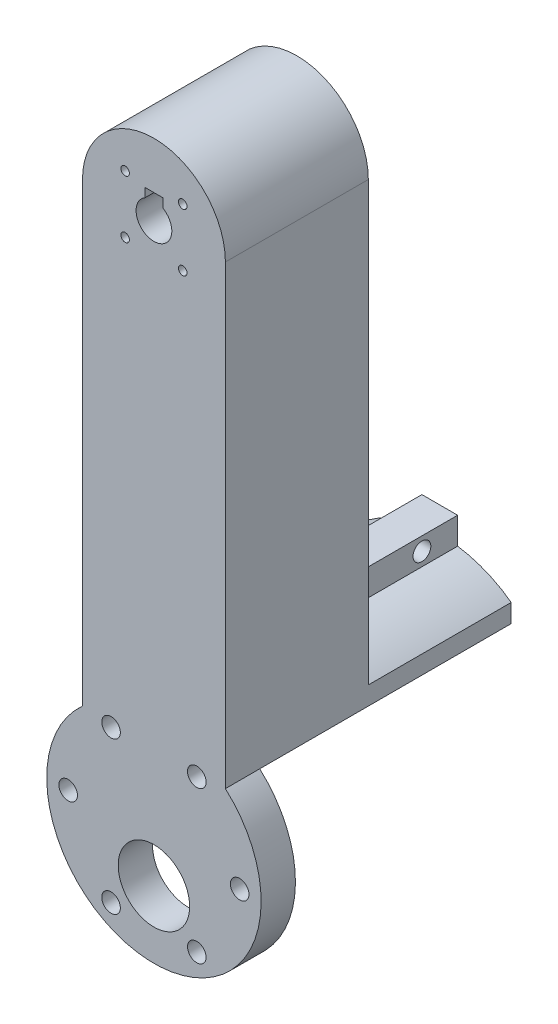
SolidWorks part; units mm, degrees
ref_plane "Front Plane" through (0, 0, 0) normal (0, 0, 1) x (1, 0, 0)
ref_plane "Top Plane" through (0, 0, 0) normal (0, 1, 0) x (1, 0, 0)
ref_plane "Right Plane" through (0, 0, 0) normal (1, 0, 0) x (0, 0, -1)
sketch "Sketch1" plane through (0, 0, 0) normal (0, 0, 1) x (1, 0, 0)
  line L0 (-5.1187, 55.9187) -> (5.1187, 45.6813) construction
  line L2 (12.7, 50.8) -> (12.7, -50.8)
  line L4 (-12.7, 50.8) -> (-12.7, -50.8)
  line L5 (12.7, 50.8) -> (-12.7, -50.8) construction
  line L6 (12.7, -50.8) -> (-12.7, 50.8) construction
  line L7 (5.1187, 55.9187) -> (-5.1187, 45.6813) construction
  line L8 (0, 50.8) -> (0, 51.7208) construction
  arc A0 (-12.7, 50.8) -> (12.7, 50.8) centre (0, 50.8) cw
  arc A1 (12.7, -50.8) -> (-12.7, -50.8) centre (0, -50.8) cw
  circle A2 centre (0, 50.8) radius 3.175
  circle A3 centre (-5.1187, 55.9187) radius 0.762
  circle A4 centre (5.1187, 55.9187) radius 0.762
  circle A5 centre (5.1187, 45.6813) radius 0.762
  circle A6 centre (-5.1187, 45.6813) radius 0.762
  point P0 (0, 0)
  point P14 (0, 50.8)
  point P15 (0, 50.8)
  point P20 (0, 0)
  point P21 (0, 0)
  dimension "D3" = 6.35
  dimension "D6" = 1.524
  dimension "D1" = 25.4
  dimension "D2" = 101.6
  dimension "D4" = 45
  dimension "D5" = 14.478
extrude "Boss-Extrude1" add sketch "Sketch1" along normal blind 25.4
sketch "Sketch2" plane through (0, 0, 0) normal (0, 0, -1) x (-1, 0, 0)
  circle A0 centre (0, -44.45) radius 19.05
  circle A1 centre (0, 50.8) radius 3.175 construction
  arc A2 (-12.7, -50.8) -> (12.7, -50.8) centre (0, -50.8) ccw construction
  circle A3 centre (0, 50.8) radius 3.175
  point P5 (0, 0)
  point P10 (0, 0)
  point P11 (0, 0)
  point P12 (0, 0)
  point P13 (0, 0)
  dimension "D1" = 38.1
extrude "Boss-Extrude2" add sketch "Sketch2" against normal blind 25.4
sketch "Sketch4" plane through (0, 0, 25.4) normal (0, 0, 1) x (1, 0, 0)
  circle A0 centre (0, -44.45) radius 19.05
  arc A1 (-12.7, -30.251) -> (12.7, -30.251) centre (0, -44.45) ccw construction
  point P5 (0, 0)
  point P6 (0, 0)
  point P7 (0, 0)
  point P9 (0, 0)
  point P10 (0, 0)
  dimension "D1" = 38.1
sketch "Sketch3" plane through (0, 0, 25.4) normal (0, 0, 1) x (1, 0, 0)
  line L0 (-15.24, -44.45) -> (15.24, -44.45) construction
  line L1 (15.24, -44.45) -> (7.62, -30.9593) construction
  line L2 (-15.24, -44.45) -> (-7.62, -30.9593) construction
  line L3 (-15.24, -44.45) -> (-7.62, -57.9407) construction
  line L4 (15.24, -44.45) -> (7.62, -57.9407) construction
  line L5 (0, -44.45) -> (0, 0) construction
  circle A0 centre (-7.62, -30.9593) radius 1.651
  circle A1 centre (7.62, -30.9593) radius 1.651
  circle A2 centre (-15.24, -44.45) radius 1.651
  circle A3 centre (-7.62, -57.9407) radius 1.651
  circle A4 centre (7.62, -57.9407) radius 1.651
  circle A5 centre (15.24, -44.45) radius 1.651
  point P10 (0, -44.45)
  dimension "D5" = 3.302
  dimension "D1" = 30.48
  dimension "D2" = 15.494
  dimension "D3" = 30.988
  dimension "D4" = 15.24
extrude "Cut-Extrude1" cut sketch "Sketch3" against normal blind 25.4
sketch "Sketch5" plane through (0, 0, 25.4) normal (0, 0, 1) x (1, 0, 0)
  circle A0 centre (0, -51.562) radius 6.35
  point P2 (0, 0)
  dimension "D1" = 12.7
  dimension "D2" = 7.112
extrude "Cut-Extrude2" cut sketch "Sketch5" against normal blind 25.4
sketch "Sketch6" plane through (0, 0, 0) normal (0, 0, -1) x (-1, 0, 0)
  line L1 (-1.5875, 55.1371) -> (1.5875, 55.1371)
  line L2 (-1.5875, 55.1371) -> (-1.5875, 53.5496)
  line L3 (-1.5875, 53.5496) -> (1.5875, 53.5496)
  line L4 (1.5875, 55.1371) -> (1.5875, 53.5496)
  circle A1 centre (0, 50.8) radius 3.175 construction
  point P4 (0, 0)
  point P5 (0, 0)
  point P9 (0, 0)
  dimension "D1" = 3.175
  dimension "D2" = 1.5875
extrude "Cut-Extrude3" cut sketch "Sketch6" against normal blind 25.4
extrude "Cut-Extrude6" cut sketch "Sketch2<2>" against normal up to surface (25.4 mm away) contours A3 up to face at (0, 54.3434, 25.4)
sketch "Sketch2<2>" plane through (0, 0, 0) normal (0, 0, -1) x (-1, 0, 0) same geometry as "Sketch2"
sketch "Sketch8" plane through (0, 0, 0) normal (0, 0, -1) x (-1, 0, 0)
  circle A0 centre (0, -44.45) radius 19.05
  arc A1 (-1.5875, 53.5496) -> (1.5875, 53.5496) centre (0, 50.8) ccw construction
  arc A2 (-1.5875, 53.5496) -> (1.5875, 53.5496) centre (0, 50.8) ccw
  point P3 (0, 0)
  point P7 (0, 0)
  circle M6 centre (0, -51.562) radius 6.35
  circle M7 centre (7.62, -30.9593) radius 1.651
  circle M8 centre (-15.24, -44.45) radius 1.651
  circle M9 centre (-7.62, -57.9407) radius 1.651
  circle M10 centre (7.62, -57.9407) radius 1.651
  circle M11 centre (15.24, -44.45) radius 1.651
  circle M12 centre (-7.62, -30.9593) radius 1.651
  arc M14 (-12.7, -30.251) -> (12.7, -30.251) centre (0, -44.45) ccw
  dimension "D1" = 38.1
extrude "Cut-Extrude4" cut sketch "Sketch8" against normal blind 19.3 contours A0 M14 M6 M8 M10 M12 M11 M9 M7 | M7 | M12 | M8 | M9 | M6 | M10 | M11 region at (0, -43.5135, 0) region at (0, -51.562, 0) region at (-7.62, -30.9593, 0) region at (15.24, -44.45, 0) region at (7.62, -57.9407, 0) region at (-7.62, -57.9407, 0) region at (-15.24, -44.45, 0) region at (7.62, -30.9593, 0)
sketch "Sketch9" plane through (0, 0, 0) normal (0, 0, -1) x (-1, 0, 0)
  line L0 (12.7, 50.8) -> (12.7, -30.251) construction
  line L1 (-12.7, -30.251) -> (-12.7, 50.8) construction
  line L2 (-12.7, -30.251) -> (-12.7, -26.9904)
  line L3 (12.7, -30.251) -> (12.7, -26.9904)
  arc A0 (-12.7, -30.251) -> (12.7, -30.251) centre (0, -44.45) cw
  arc A1 (-12.7, -26.9904) -> (12.7, -26.9904) centre (0, -44.45) cw
  dimension "D1" = 2.54
extrude "Boss-Extrude3" add sketch "Sketch9" along normal blind 25.4
sketch "Sketch10" plane through (0, 0, 0) normal (0, 0, -1) x (-1, 0, 0)
  line L1 (-3.175, -18.3322) -> (3.175, -18.3322)
  line L2 (-3.175, -18.3322) -> (-3.175, -23.0947)
  line L3 (-3.175, -23.0947) -> (3.175, -23.0947)
  line L4 (3.175, -18.3322) -> (3.175, -23.0947)
  arc A0 (12.7, -26.9904) -> (-12.7, -26.9904) centre (0, -44.45) ccw construction
  point P4 (0, -18.3322)
  dimension "D1" = 6.35
  dimension "D2" = 4.7625
extrude "Boss-Extrude4" add sketch "Sketch10" along normal up to surface (25.4 mm away) up to face at (0, -26.3753, -25.4)
sketch "Sketch11" plane through (3.175, 0, 0) normal (1, 0, 0) x (0, 0, -1)
  line L0 (24.0343, -18.3322) -> (24.0343, -23.0947) construction
  line L1 (25.4, -18.3322) -> (0, -18.3322) construction
  line L2 (25.4, -23.0947) -> (0, -23.0947) construction
  line L3 (0, -26.9904) -> (0, 50.8) construction
  line L4 (25.4, -23.0947) -> (25.4, -18.3322) construction
  circle A0 centre (6.35, -20.7135) radius 1.5875
  circle A1 centre (19.05, -20.7135) radius 1.5875
  point P9 (24.0343, -20.7135)
  dimension "D1" = 3.175
  dimension "D2" = 6.35
  dimension "D3" = 6.35
extrude "Cut-Extrude5" cut sketch "Sketch11" against normal through all
ref_plane "Plane1" through (0, 0, 12.7) normal (0, 0, 1) x (1, 0, 0)
ref_axis "Axis1" through (0, 50.8, 25.4) along (0, 0, -1)
ref_point "Point1"
ref_plane "Plane2" through (0, 0, 37.2197) normal (0, 0, -1) x (-1, 0, 0)
ref_axis "Axis2" through (0, -51.562, 19.3) along (0, 0, 1)
ref_point "wheel orgin point"
